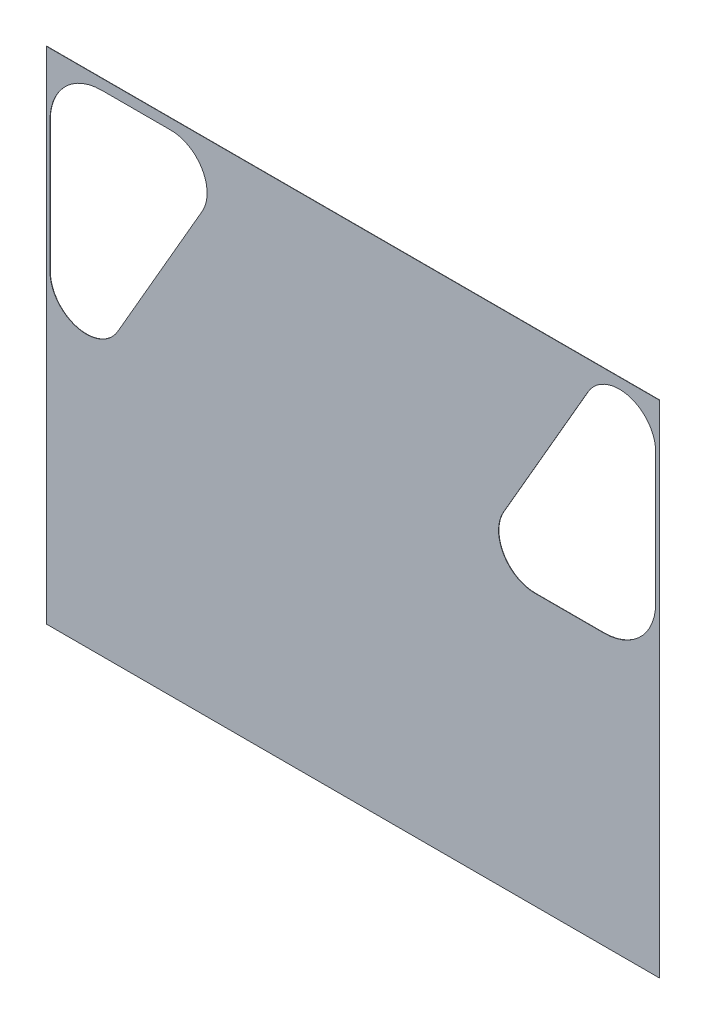
SolidWorks part; units mm, degrees
ref_plane "Front Plane" through (0, 0, 0) normal (0, 0, 1) x (1, 0, 0)
ref_plane "Top Plane" through (0, 0, 0) normal (0, 1, 0) x (1, 0, 0)
ref_plane "Right Plane" through (0, 0, 0) normal (1, 0, 0) x (0, 0, -1)
sketch "Sketch1" plane through (0, 0, 0) normal (0, 0, 1) x (1, 0, 0)
  line L1 (0, 0) -> (1991, 0)
  line L2 (0, 0) -> (0, 1625)
  line L3 (0, 1625) -> (1991, 1625)
  line L4 (1991, 0) -> (1991, 1625)
  dimension "D1" = 1991
  dimension "D2" = 1625
extrude "Boss-Extrude1" add sketch "Sketch1" along normal blind 1
extrude "Cut-Extrude1" cut sketch "Sketch2" against normal through all
sketch "Sketch2" plane through (259.9635, -561.6168, 1) normal (0, 0, 1) x (1, 0, 0)
  line L0 (1498.8454, 2093.6165) -> (1224.6054, 1618.6165)
  line L1 (1326.7965, 1441.6168) -> (1551.0365, 1441.6168)
  line L2 (1719.0365, 1609.6168) -> (1719.0365, 2034.6168)
  line L5 (-247.9635, 1984.6168) -> (-247.9635, 1559.6168)
  line L6 (-27.7724, 1500.617) -> (246.4676, 1975.617)
  line L7 (144.2765, 2152.6168) -> (-79.9635, 2152.6168)
  arc A0 (1551.0365, 1441.6168) -> (1719.0365, 1609.6168) centre (1551.0365, 1609.6168) ccw
  arc A1 (1498.8454, 2093.6165) -> (1719.0365, 2034.6168) centre (1601.0365, 2034.6168) cw
  arc A2 (1224.6054, 1618.6165) -> (1326.7965, 1441.6168) centre (1326.7965, 1559.6168) ccw
  arc A3 (-247.9635, 1559.6168) -> (-27.7724, 1500.617) centre (-129.9635, 1559.6168) ccw
  arc A4 (246.4676, 1975.617) -> (144.2765, 2152.6168) centre (144.2765, 2034.6168) ccw
  arc A5 (-247.9635, 1984.6168) -> (-79.9635, 2152.6168) centre (-79.9635, 1984.6168) cw
